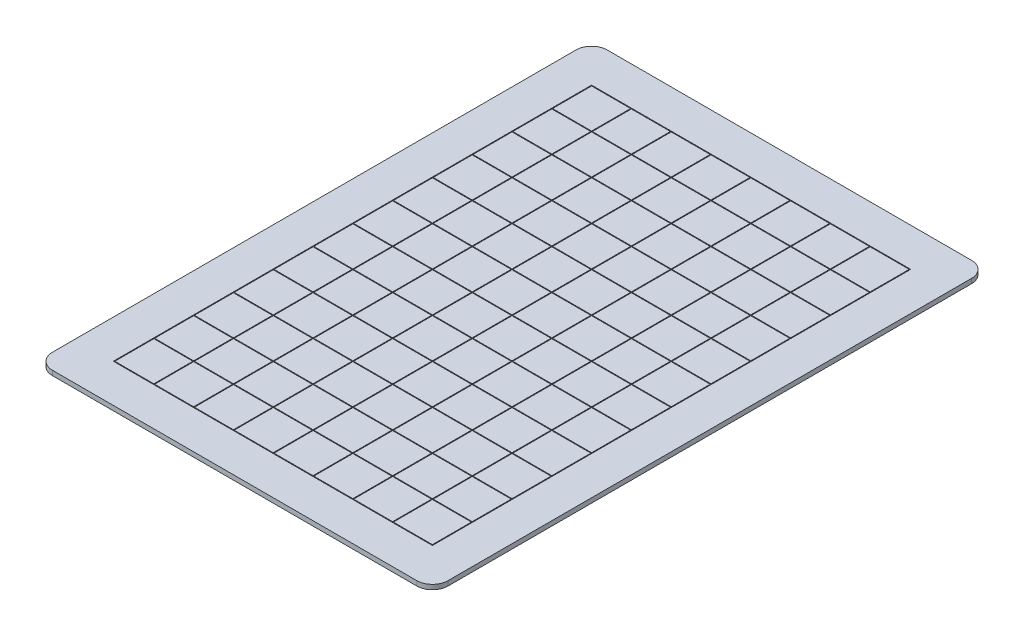
SolidWorks part; units mm, degrees
ref_plane "Front Plane" through (0, 0, 0) normal (0, 0, 1) x (1, 0, 0)
ref_plane "Top Plane" through (0, 0, 0) normal (0, 1, 0) x (1, 0, 0)
ref_plane "Right Plane" through (0, 0, 0) normal (1, 0, 0) x (0, 0, -1)
sketch "Sketch1" plane through (0, 0, 0) normal (0, 1, 0) x (1, 0, 0)
  line L1 (0, 0) -> (253.5, 0)
  line L2 (0, 0) -> (0, 355.5)
  line L3 (0, 355.5) -> (253.5, 355.5)
  line L4 (253.5, 0) -> (253.5, 355.5)
  dimension "D1" = 253.5
  dimension "D2" = 355.5
extrude "Boss-Extrude1" add sketch "Sketch1" along normal blind 3
sketch "Sketch2" plane through (0, 3, 0) normal (0, 1, 0) x (1, 0, 0)
  line L0 (0, 0) -> (253.5, 0) construction
  line L1 (25, 50) -> (50, 50)
  line L2 (25, 50) -> (25, 25)
  line L3 (25, 25) -> (50, 25)
  line L4 (50, 50) -> (50, 25)
  line L5 (0, 355.5) -> (0, 0) construction
  line L6 (50.5, 50) -> (50.5, 25)
  line L7 (50.5, 50) -> (75.5, 50)
  line L8 (75.5, 50) -> (75.5, 25)
  line L9 (50.5, 25) -> (75.5, 25)
  line L10 (76, 50) -> (76, 25)
  line L11 (76, 50) -> (101, 50)
  line L12 (101, 50) -> (101, 25)
  line L13 (76, 25) -> (101, 25)
  line L14 (101.5, 50) -> (101.5, 25)
  line L15 (101.5, 50) -> (126.5, 50)
  line L16 (126.5, 50) -> (126.5, 25)
  line L17 (101.5, 25) -> (126.5, 25)
  line L18 (127, 50) -> (127, 25)
  line L19 (127, 50) -> (152, 50)
  line L20 (152, 50) -> (152, 25)
  line L21 (127, 25) -> (152, 25)
  line L22 (152.5, 50) -> (152.5, 25)
  line L23 (152.5, 50) -> (177.5, 50)
  line L24 (177.5, 50) -> (177.5, 25)
  line L25 (152.5, 25) -> (177.5, 25)
  line L26 (178, 50) -> (178, 25)
  line L27 (178, 50) -> (203, 50)
  line L28 (203, 50) -> (203, 25)
  line L29 (178, 25) -> (203, 25)
  line L30 (203.5, 50) -> (203.5, 25)
  line L31 (203.5, 50) -> (228.5, 50)
  line L32 (228.5, 50) -> (228.5, 25)
  line L33 (203.5, 25) -> (228.5, 25)
  line L34 (50.5, 75.5) -> (50.5, 50.5)
  line L35 (50.5, 75.5) -> (75.5, 75.5)
  line L36 (75.5, 75.5) -> (75.5, 50.5)
  line L37 (50.5, 50.5) -> (75.5, 50.5)
  line L38 (76, 75.5) -> (76, 50.5)
  line L39 (76, 75.5) -> (101, 75.5)
  line L40 (101, 75.5) -> (101, 50.5)
  line L41 (76, 50.5) -> (101, 50.5)
  line L42 (101.5, 75.5) -> (101.5, 50.5)
  line L43 (101.5, 75.5) -> (126.5, 75.5)
  line L44 (126.5, 75.5) -> (126.5, 50.5)
  line L45 (101.5, 50.5) -> (126.5, 50.5)
  line L46 (127, 75.5) -> (127, 50.5)
  line L47 (127, 75.5) -> (152, 75.5)
  line L48 (152, 75.5) -> (152, 50.5)
  line L49 (127, 50.5) -> (152, 50.5)
  line L50 (152.5, 75.5) -> (152.5, 50.5)
  line L51 (152.5, 75.5) -> (177.5, 75.5)
  line L52 (177.5, 75.5) -> (177.5, 50.5)
  line L53 (152.5, 50.5) -> (177.5, 50.5)
  line L54 (178, 75.5) -> (178, 50.5)
  line L55 (178, 75.5) -> (203, 75.5)
  line L56 (203, 75.5) -> (203, 50.5)
  line L57 (178, 50.5) -> (203, 50.5)
  line L58 (203.5, 75.5) -> (203.5, 50.5)
  line L59 (203.5, 75.5) -> (228.5, 75.5)
  line L60 (228.5, 75.5) -> (228.5, 50.5)
  line L61 (203.5, 50.5) -> (228.5, 50.5)
  line L62 (50.5, 101) -> (50.5, 76)
  line L63 (50.5, 101) -> (75.5, 101)
  line L64 (75.5, 101) -> (75.5, 76)
  line L65 (50.5, 76) -> (75.5, 76)
  line L66 (76, 101) -> (76, 76)
  line L67 (76, 101) -> (101, 101)
  line L68 (101, 101) -> (101, 76)
  line L69 (76, 76) -> (101, 76)
  line L70 (101.5, 101) -> (101.5, 76)
  line L71 (101.5, 101) -> (126.5, 101)
  line L72 (126.5, 101) -> (126.5, 76)
  line L73 (101.5, 76) -> (126.5, 76)
  line L74 (127, 101) -> (127, 76)
  line L75 (127, 101) -> (152, 101)
  line L76 (152, 101) -> (152, 76)
  line L77 (127, 76) -> (152, 76)
  line L78 (152.5, 101) -> (152.5, 76)
  line L79 (152.5, 101) -> (177.5, 101)
  line L80 (177.5, 101) -> (177.5, 76)
  line L81 (152.5, 76) -> (177.5, 76)
  line L82 (178, 101) -> (178, 76)
  line L83 (178, 101) -> (203, 101)
  line L84 (203, 101) -> (203, 76)
  line L85 (178, 76) -> (203, 76)
  line L86 (203.5, 101) -> (203.5, 76)
  line L87 (203.5, 101) -> (228.5, 101)
  line L88 (228.5, 101) -> (228.5, 76)
  line L89 (203.5, 76) -> (228.5, 76)
  line L90 (50.5, 126.5) -> (50.5, 101.5)
  line L91 (50.5, 126.5) -> (75.5, 126.5)
  line L92 (75.5, 126.5) -> (75.5, 101.5)
  line L93 (50.5, 101.5) -> (75.5, 101.5)
  line L94 (76, 126.5) -> (76, 101.5)
  line L95 (76, 126.5) -> (101, 126.5)
  line L96 (101, 126.5) -> (101, 101.5)
  line L97 (76, 101.5) -> (101, 101.5)
  line L98 (101.5, 126.5) -> (101.5, 101.5)
  line L99 (101.5, 126.5) -> (126.5, 126.5)
  line L100 (126.5, 126.5) -> (126.5, 101.5)
  line L101 (101.5, 101.5) -> (126.5, 101.5)
  line L102 (127, 126.5) -> (127, 101.5)
  line L103 (127, 126.5) -> (152, 126.5)
  line L104 (152, 126.5) -> (152, 101.5)
  line L105 (127, 101.5) -> (152, 101.5)
  line L106 (152.5, 126.5) -> (152.5, 101.5)
  line L107 (152.5, 126.5) -> (177.5, 126.5)
  line L108 (177.5, 126.5) -> (177.5, 101.5)
  line L109 (152.5, 101.5) -> (177.5, 101.5)
  line L110 (178, 126.5) -> (178, 101.5)
  line L111 (178, 126.5) -> (203, 126.5)
  line L112 (203, 126.5) -> (203, 101.5)
  line L113 (178, 101.5) -> (203, 101.5)
  line L114 (203.5, 126.5) -> (203.5, 101.5)
  line L115 (203.5, 126.5) -> (228.5, 126.5)
  line L116 (228.5, 126.5) -> (228.5, 101.5)
  line L117 (203.5, 101.5) -> (228.5, 101.5)
  line L118 (50.5, 152) -> (50.5, 127)
  line L119 (50.5, 152) -> (75.5, 152)
  line L120 (75.5, 152) -> (75.5, 127)
  line L121 (50.5, 127) -> (75.5, 127)
  line L122 (76, 152) -> (76, 127)
  line L123 (76, 152) -> (101, 152)
  line L124 (101, 152) -> (101, 127)
  line L125 (76, 127) -> (101, 127)
  line L126 (101.5, 152) -> (101.5, 127)
  line L127 (101.5, 152) -> (126.5, 152)
  line L128 (126.5, 152) -> (126.5, 127)
  line L129 (101.5, 127) -> (126.5, 127)
  line L130 (127, 152) -> (127, 127)
  line L131 (127, 152) -> (152, 152)
  line L132 (152, 152) -> (152, 127)
  line L133 (127, 127) -> (152, 127)
  line L134 (152.5, 152) -> (152.5, 127)
  line L135 (152.5, 152) -> (177.5, 152)
  line L136 (177.5, 152) -> (177.5, 127)
  line L137 (152.5, 127) -> (177.5, 127)
  line L138 (178, 152) -> (178, 127)
  line L139 (178, 152) -> (203, 152)
  line L140 (203, 152) -> (203, 127)
  line L141 (178, 127) -> (203, 127)
  line L142 (203.5, 152) -> (203.5, 127)
  line L143 (203.5, 152) -> (228.5, 152)
  line L144 (228.5, 152) -> (228.5, 127)
  line L145 (203.5, 127) -> (228.5, 127)
  line L146 (50.5, 177.5) -> (50.5, 152.5)
  line L147 (50.5, 177.5) -> (75.5, 177.5)
  line L148 (75.5, 177.5) -> (75.5, 152.5)
  line L149 (50.5, 152.5) -> (75.5, 152.5)
  line L150 (76, 177.5) -> (76, 152.5)
  line L151 (76, 177.5) -> (101, 177.5)
  line L152 (101, 177.5) -> (101, 152.5)
  line L153 (76, 152.5) -> (101, 152.5)
  line L154 (101.5, 177.5) -> (101.5, 152.5)
  line L155 (101.5, 177.5) -> (126.5, 177.5)
  line L156 (126.5, 177.5) -> (126.5, 152.5)
  line L157 (101.5, 152.5) -> (126.5, 152.5)
  line L158 (127, 177.5) -> (127, 152.5)
  line L159 (127, 177.5) -> (152, 177.5)
  line L160 (152, 177.5) -> (152, 152.5)
  line L161 (127, 152.5) -> (152, 152.5)
  line L162 (152.5, 177.5) -> (152.5, 152.5)
  line L163 (152.5, 177.5) -> (177.5, 177.5)
  line L164 (177.5, 177.5) -> (177.5, 152.5)
  line L165 (152.5, 152.5) -> (177.5, 152.5)
  line L166 (178, 177.5) -> (178, 152.5)
  line L167 (178, 177.5) -> (203, 177.5)
  line L168 (203, 177.5) -> (203, 152.5)
  line L169 (178, 152.5) -> (203, 152.5)
  line L170 (203.5, 177.5) -> (203.5, 152.5)
  line L171 (203.5, 177.5) -> (228.5, 177.5)
  line L172 (228.5, 177.5) -> (228.5, 152.5)
  line L173 (203.5, 152.5) -> (228.5, 152.5)
  line L174 (50.5, 203) -> (50.5, 178)
  line L175 (50.5, 203) -> (75.5, 203)
  line L176 (75.5, 203) -> (75.5, 178)
  line L177 (50.5, 178) -> (75.5, 178)
  line L178 (76, 203) -> (76, 178)
  line L179 (76, 203) -> (101, 203)
  line L180 (101, 203) -> (101, 178)
  line L181 (76, 178) -> (101, 178)
  line L182 (101.5, 203) -> (101.5, 178)
  line L183 (101.5, 203) -> (126.5, 203)
  line L184 (126.5, 203) -> (126.5, 178)
  line L185 (101.5, 178) -> (126.5, 178)
  line L186 (127, 203) -> (127, 178)
  line L187 (127, 203) -> (152, 203)
  line L188 (152, 203) -> (152, 178)
  line L189 (127, 178) -> (152, 178)
  line L190 (152.5, 203) -> (152.5, 178)
  line L191 (152.5, 203) -> (177.5, 203)
  line L192 (177.5, 203) -> (177.5, 178)
  line L193 (152.5, 178) -> (177.5, 178)
  line L194 (178, 203) -> (178, 178)
  line L195 (178, 203) -> (203, 203)
  line L196 (203, 203) -> (203, 178)
  line L197 (178, 178) -> (203, 178)
  line L198 (203.5, 203) -> (203.5, 178)
  line L199 (203.5, 203) -> (228.5, 203)
  line L200 (228.5, 203) -> (228.5, 178)
  line L201 (203.5, 178) -> (228.5, 178)
  line L202 (50.5, 228.5) -> (50.5, 203.5)
  line L203 (50.5, 228.5) -> (75.5, 228.5)
  line L204 (75.5, 228.5) -> (75.5, 203.5)
  line L205 (50.5, 203.5) -> (75.5, 203.5)
  line L206 (76, 228.5) -> (76, 203.5)
  line L207 (76, 228.5) -> (101, 228.5)
  line L208 (101, 228.5) -> (101, 203.5)
  line L209 (76, 203.5) -> (101, 203.5)
  line L210 (101.5, 228.5) -> (101.5, 203.5)
  line L211 (101.5, 228.5) -> (126.5, 228.5)
  line L212 (126.5, 228.5) -> (126.5, 203.5)
  line L213 (101.5, 203.5) -> (126.5, 203.5)
  line L214 (127, 228.5) -> (127, 203.5)
  line L215 (127, 228.5) -> (152, 228.5)
  line L216 (152, 228.5) -> (152, 203.5)
  line L217 (127, 203.5) -> (152, 203.5)
  line L218 (152.5, 228.5) -> (152.5, 203.5)
  line L219 (152.5, 228.5) -> (177.5, 228.5)
  line L220 (177.5, 228.5) -> (177.5, 203.5)
  line L221 (152.5, 203.5) -> (177.5, 203.5)
  line L222 (178, 228.5) -> (178, 203.5)
  line L223 (178, 228.5) -> (203, 228.5)
  line L224 (203, 228.5) -> (203, 203.5)
  line L225 (178, 203.5) -> (203, 203.5)
  line L226 (203.5, 228.5) -> (203.5, 203.5)
  line L227 (203.5, 228.5) -> (228.5, 228.5)
  line L228 (228.5, 228.5) -> (228.5, 203.5)
  line L229 (203.5, 203.5) -> (228.5, 203.5)
  line L230 (50.5, 254) -> (50.5, 229)
  line L231 (50.5, 254) -> (75.5, 254)
  line L232 (75.5, 254) -> (75.5, 229)
  line L233 (50.5, 229) -> (75.5, 229)
  line L234 (76, 254) -> (76, 229)
  line L235 (76, 254) -> (101, 254)
  line L236 (101, 254) -> (101, 229)
  line L237 (76, 229) -> (101, 229)
  line L238 (101.5, 254) -> (101.5, 229)
  line L239 (101.5, 254) -> (126.5, 254)
  line L240 (126.5, 254) -> (126.5, 229)
  line L241 (101.5, 229) -> (126.5, 229)
  line L242 (127, 254) -> (127, 229)
  line L243 (127, 254) -> (152, 254)
  line L244 (152, 254) -> (152, 229)
  line L245 (127, 229) -> (152, 229)
  line L246 (152.5, 254) -> (152.5, 229)
  line L247 (152.5, 254) -> (177.5, 254)
  line L248 (177.5, 254) -> (177.5, 229)
  line L249 (152.5, 229) -> (177.5, 229)
  line L250 (178, 254) -> (178, 229)
  line L251 (178, 254) -> (203, 254)
  line L252 (203, 254) -> (203, 229)
  line L253 (178, 229) -> (203, 229)
  line L254 (203.5, 254) -> (203.5, 229)
  line L255 (203.5, 254) -> (228.5, 254)
  line L256 (228.5, 254) -> (228.5, 229)
  line L257 (203.5, 229) -> (228.5, 229)
  line L258 (50.5, 279.5) -> (50.5, 254.5)
  line L259 (50.5, 279.5) -> (75.5, 279.5)
  line L260 (75.5, 279.5) -> (75.5, 254.5)
  line L261 (50.5, 254.5) -> (75.5, 254.5)
  line L262 (76, 279.5) -> (76, 254.5)
  line L263 (76, 279.5) -> (101, 279.5)
  line L264 (101, 279.5) -> (101, 254.5)
  line L265 (76, 254.5) -> (101, 254.5)
  line L266 (101.5, 279.5) -> (101.5, 254.5)
  line L267 (101.5, 279.5) -> (126.5, 279.5)
  line L268 (126.5, 279.5) -> (126.5, 254.5)
  line L269 (101.5, 254.5) -> (126.5, 254.5)
  line L270 (127, 279.5) -> (127, 254.5)
  line L271 (127, 279.5) -> (152, 279.5)
  line L272 (152, 279.5) -> (152, 254.5)
  line L273 (127, 254.5) -> (152, 254.5)
  line L274 (152.5, 279.5) -> (152.5, 254.5)
  line L275 (152.5, 279.5) -> (177.5, 279.5)
  line L276 (177.5, 279.5) -> (177.5, 254.5)
  line L277 (152.5, 254.5) -> (177.5, 254.5)
  line L278 (178, 279.5) -> (178, 254.5)
  line L279 (178, 279.5) -> (203, 279.5)
  line L280 (203, 279.5) -> (203, 254.5)
  line L281 (178, 254.5) -> (203, 254.5)
  line L282 (203.5, 279.5) -> (203.5, 254.5)
  line L283 (203.5, 279.5) -> (228.5, 279.5)
  line L284 (228.5, 279.5) -> (228.5, 254.5)
  line L285 (203.5, 254.5) -> (228.5, 254.5)
  line L286 (50.5, 305) -> (50.5, 280)
  line L287 (50.5, 305) -> (75.5, 305)
  line L288 (75.5, 305) -> (75.5, 280)
  line L289 (50.5, 280) -> (75.5, 280)
  line L290 (76, 305) -> (76, 280)
  line L291 (76, 305) -> (101, 305)
  line L292 (101, 305) -> (101, 280)
  line L293 (76, 280) -> (101, 280)
  line L294 (101.5, 305) -> (101.5, 280)
  line L295 (101.5, 305) -> (126.5, 305)
  line L296 (126.5, 305) -> (126.5, 280)
  line L297 (101.5, 280) -> (126.5, 280)
  line L298 (127, 305) -> (127, 280)
  line L299 (127, 305) -> (152, 305)
  line L300 (152, 305) -> (152, 280)
  line L301 (127, 280) -> (152, 280)
  line L302 (152.5, 305) -> (152.5, 280)
  line L303 (152.5, 305) -> (177.5, 305)
  line L304 (177.5, 305) -> (177.5, 280)
  line L305 (152.5, 280) -> (177.5, 280)
  line L306 (178, 305) -> (178, 280)
  line L307 (178, 305) -> (203, 305)
  line L308 (203, 305) -> (203, 280)
  line L309 (178, 280) -> (203, 280)
  line L310 (203.5, 305) -> (203.5, 280)
  line L311 (203.5, 305) -> (228.5, 305)
  line L312 (228.5, 305) -> (228.5, 280)
  line L313 (203.5, 280) -> (228.5, 280)
  line L314 (50.5, 330.5) -> (50.5, 305.5)
  line L315 (50.5, 330.5) -> (75.5, 330.5)
  line L316 (75.5, 330.5) -> (75.5, 305.5)
  line L317 (50.5, 305.5) -> (75.5, 305.5)
  line L318 (76, 330.5) -> (76, 305.5)
  line L319 (76, 330.5) -> (101, 330.5)
  line L320 (101, 330.5) -> (101, 305.5)
  line L321 (76, 305.5) -> (101, 305.5)
  line L322 (101.5, 330.5) -> (101.5, 305.5)
  line L323 (101.5, 330.5) -> (126.5, 330.5)
  line L324 (126.5, 330.5) -> (126.5, 305.5)
  line L325 (101.5, 305.5) -> (126.5, 305.5)
  line L326 (127, 330.5) -> (127, 305.5)
  line L327 (127, 330.5) -> (152, 330.5)
  line L328 (152, 330.5) -> (152, 305.5)
  line L329 (127, 305.5) -> (152, 305.5)
  line L330 (152.5, 330.5) -> (152.5, 305.5)
  line L331 (152.5, 330.5) -> (177.5, 330.5)
  line L332 (177.5, 330.5) -> (177.5, 305.5)
  line L333 (152.5, 305.5) -> (177.5, 305.5)
  line L334 (178, 330.5) -> (178, 305.5)
  line L335 (178, 330.5) -> (203, 330.5)
  line L336 (203, 330.5) -> (203, 305.5)
  line L337 (178, 305.5) -> (203, 305.5)
  line L338 (203.5, 330.5) -> (203.5, 305.5)
  line L339 (203.5, 330.5) -> (228.5, 330.5)
  line L340 (228.5, 330.5) -> (228.5, 305.5)
  line L341 (203.5, 305.5) -> (228.5, 305.5)
  line L342 (25, 75.5) -> (25, 50.5)
  line L343 (25, 75.5) -> (50, 75.5)
  line L344 (50, 75.5) -> (50, 50.5)
  line L345 (25, 50.5) -> (50, 50.5)
  line L346 (25, 101) -> (25, 76)
  line L347 (25, 101) -> (50, 101)
  line L348 (50, 101) -> (50, 76)
  line L349 (25, 76) -> (50, 76)
  line L350 (25, 126.5) -> (25, 101.5)
  line L351 (25, 126.5) -> (50, 126.5)
  line L352 (50, 126.5) -> (50, 101.5)
  line L353 (25, 101.5) -> (50, 101.5)
  line L354 (25, 152) -> (25, 127)
  line L355 (25, 152) -> (50, 152)
  line L356 (50, 152) -> (50, 127)
  line L357 (25, 127) -> (50, 127)
  line L358 (25, 177.5) -> (25, 152.5)
  line L359 (25, 177.5) -> (50, 177.5)
  line L360 (50, 177.5) -> (50, 152.5)
  line L361 (25, 152.5) -> (50, 152.5)
  line L362 (25, 203) -> (25, 178)
  line L363 (25, 203) -> (50, 203)
  line L364 (50, 203) -> (50, 178)
  line L365 (25, 178) -> (50, 178)
  line L366 (25, 228.5) -> (25, 203.5)
  line L367 (25, 228.5) -> (50, 228.5)
  line L368 (50, 228.5) -> (50, 203.5)
  line L369 (25, 203.5) -> (50, 203.5)
  line L370 (25, 254) -> (25, 229)
  line L371 (25, 254) -> (50, 254)
  line L372 (50, 254) -> (50, 229)
  line L373 (25, 229) -> (50, 229)
  line L374 (25, 279.5) -> (25, 254.5)
  line L375 (25, 279.5) -> (50, 279.5)
  line L376 (50, 279.5) -> (50, 254.5)
  line L377 (25, 254.5) -> (50, 254.5)
  line L378 (25, 305) -> (25, 280)
  line L379 (25, 305) -> (50, 305)
  line L380 (50, 305) -> (50, 280)
  line L381 (25, 280) -> (50, 280)
  line L382 (25, 330.5) -> (25, 305.5)
  line L383 (25, 330.5) -> (50, 330.5)
  line L384 (50, 330.5) -> (50, 305.5)
  line L385 (25, 305.5) -> (50, 305.5)
  line L387 (24.5, 331) -> (229, 331)
  line L388 (24.5, 331) -> (24.5, 24.5)
  line L389 (24.5, 24.5) -> (229, 24.5)
  line L390 (229, 331) -> (229, 24.5)
  dimension "D1" = 25
  dimension "D2" = 25
  dimension "D3" = 25
  dimension "D4" = 25
  dimension "D7" = 0.5
  dimension "D8" = 0.5
  dimension "D9" = 0.5
  dimension "D10" = 0.5
  dimension "D11" = 0.5
  dimension "D5" = 8
  dimension "D6" = 12
extrude "Cut-Extrude1" cut sketch "Sketch2" against normal blind 0.5
sketch "Sketch4" plane through (0, 0, 0) normal (0, -1, 0) x (1, 0, 0)
  line L0 (0, -355.5) -> (0, 0) construction
  line L1 (0, 0) -> (253.5, 0) construction
  line L2 (253.5, -355.5) -> (0, -355.5) construction
  line L3 (0, 0) -> (253.5, 0)
  line L4 (253.5, -355.5) -> (0, -355.5)
  line L5 (126.75, -355.5) -> (126.75, 0)
  line L6 (253.5, 0) -> (253.5, -355.5) construction
  line L7 (0, -355.5) -> (0, 0) construction
  line L8 (253.5, 0) -> (253.5, -355.5)
  line L9 (0, -355.5) -> (0, 0)
  line L10 (0, -177.75) -> (253.5, -177.75)
  circle A0 centre (6, -6) radius 1.6
  circle A1 centre (6, -91.875) radius 1.6
  circle A2 centre (6, -177.75) radius 1.6
  circle A3 centre (6, -263.625) radius 1.6
  circle A4 centre (6, -349.5) radius 1.6
  circle A5 centre (247.5, -6) radius 1.6
  circle A6 centre (247.5, -91.875) radius 1.6
  circle A7 centre (247.5, -177.75) radius 1.6
  circle A8 centre (247.5, -263.625) radius 1.6
  circle A10 centre (86.5, -349.5) radius 1.6
  circle A11 centre (167, -349.5) radius 1.6
  circle A12 centre (247.5, -349.5) radius 1.6
  circle A13 centre (167, -6) radius 1.6
  circle A14 centre (86.5, -6) radius 1.6
  dimension "D1" = 3.2
  dimension "D2" = 6
  dimension "D3" = 6
  dimension "D5" = 6
  dimension "D7" = 6
  dimension "D4" = 5
  dimension "D6" = 4
extrude "Cut-Extrude2" cut sketch "Sketch4" against normal blind 1.2 contours A14 | A0 | A13 | A5 | A6 | A7 L10 | A7 L10 | A8 | A12 | A11 | A10 | A4 | A3 | L10 A2 | L10 A2 | A1 region at (6, 0, -177.0709) region at (6, 0, -178.4291) region at (247.5, 0, -177.0709) region at (247.5, 0, -178.4291) region at (6, 0, -6) region at (6, 0, -91.875) region at (6, 0, -263.625) region at (6, 0, -349.5) region at (247.5, 0, -6) region at (247.5, 0, -91.875) region at (247.5, 0, -263.625) region at (86.5, 0, -349.5) region at (167, 0, -349.5) region at (247.5, 0, -349.5) region at (167, 0, -6) region at (86.5, 0, -6)
fillet "Fillet1" radius 10 4 edges at (253.5, 1.5, 0) (0, 1.5, 0) (0, 1.5, -355.5) (253.5, 1.5, -355.5)
